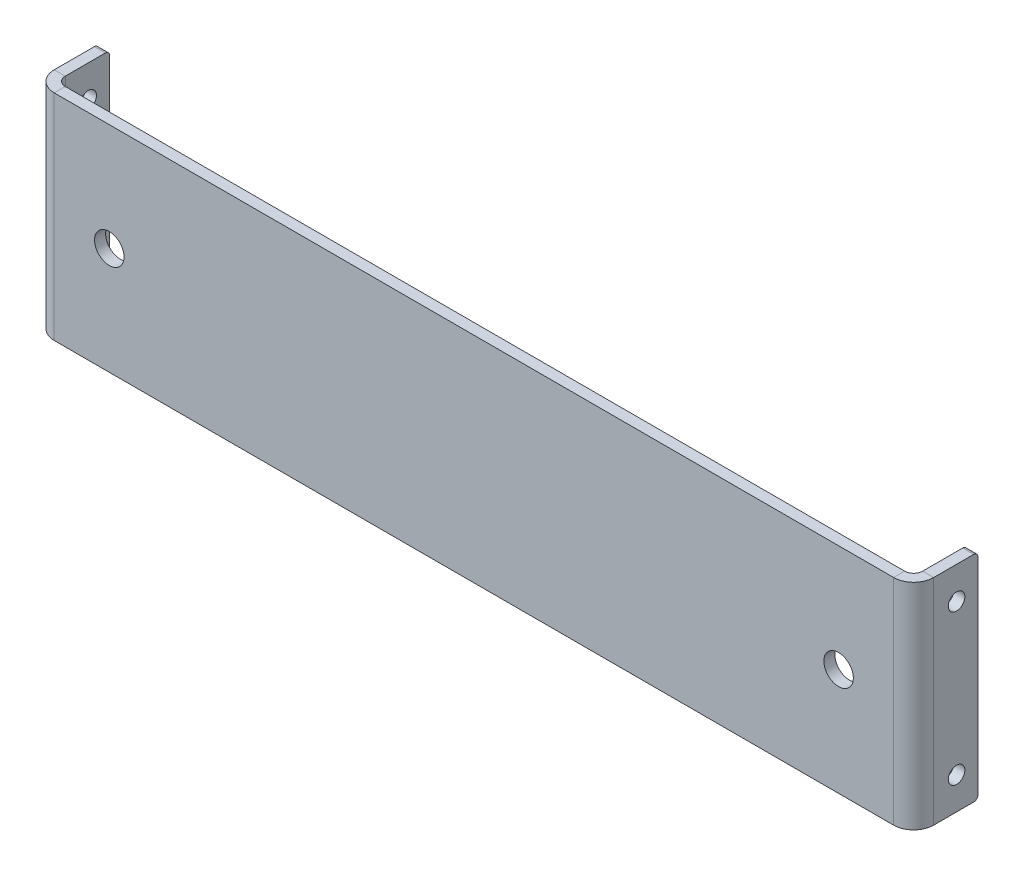
SolidWorks part; units mm, degrees
note: The reader was unsure of these and kept them because the rebuilt part matched: flange length of "Edge-Flange1".
ref_plane "Front Plane" through (0, 0, 0) normal (0, 0, 1) x (1, 0, 0)
ref_plane "Top Plane" through (0, 0, 0) normal (0, 1, 0) x (1, 0, 0)
ref_plane "Right Plane" through (0, 0, 0) normal (1, 0, 0) x (0, 0, -1)
sketch "Sketch1" plane through (0, 0, 0) normal (0, 0, 1) x (1, 0, 0)
  line L1 (-130.175, -31.75) -> (130.175, -31.75)
  line L2 (-130.175, -31.75) -> (-130.175, 31.75)
  line L3 (-130.175, 31.75) -> (130.175, 31.75)
  line L4 (130.175, -31.75) -> (130.175, 31.75)
  line L5 (-130.175, -31.75) -> (130.175, 31.75) construction
  line L6 (-130.175, 31.75) -> (130.175, -31.75) construction
  point P0 (0, 0)
  dimension "D1" = 260.35
  dimension "D2" = 63.5
base flange "Base-Flange1" sketch "Sketch1" thickness 3.2639 reverse thickness direction no parameters "D1"=2.6568
edge flange "Edge-Flange1" sketch "Sketch10" flange profiles "Sketch10", "Sketch11" flange angle 90 flange length 19.05 flange position material inside bend radius 2.6568 thickness 3.2639 relief rectangular parameters "D6"=10, "D8"=1
sketch "Sketch10" plane through (130.175, 0, -3.2639) normal (-1, 0, 0) x (0, 1, 0)
  line L2 (-31.75, 0) -> (-31.75, 15.7861)
  line L3 (-31.75, 15.7861) -> (31.75, 15.7861)
  line L4 (31.75, 15.7861) -> (31.75, 0)
  line L5 (31.75, 0) -> (-31.75, 0) construction
  line L6 (31.75, 0) -> (-31.75, 0)
sketch "Sketch11" plane through (-130.175, 0, -3.2639) normal (1, 0, 0) x (0, -1, 0)
  line L0 (31.75, 0) -> (-31.75, 0) construction
  line L1 (31.75, 0) -> (-31.75, 0)
  line L2 (31.75, 0) -> (31.75, 15.7861)
  line L3 (31.75, 15.7861) -> (-31.75, 15.7861)
  line L4 (-31.75, 15.7861) -> (-31.75, 0)
bend "EdgeBend1" bend radius 2.6568 bend angle 90 parameters "D5"=1
bend "EdgeBend2" bend radius 2.6568 bend angle 90 parameters "D5"=2
hole_wizard "#10 (0.1935) Diameter Hole1" positions "Sketch12" profile "Sketch13" hole size "#10" standard "ANSI Inch" end condition through all
sketch "Sketch12" plane through (130.175, 0, 0) normal (1, 0, 0) x (0, 0, -1)
  line L0 (0, -31.75) -> (0, 31.75) construction
  line L1 (5.9207, 31.75) -> (19.05, 31.75) construction
  line L2 (19.05, -31.75) -> (5.9207, -31.75) construction
  point P0 (12.7, 22.225)
  point P2 (12.7, -22.225)
  dimension "D1" = 12.7
  dimension "D2" = 9.525
  dimension "D3" = 9.525
sketch "Sketch13" plane through (130.175, 22.225, -12.7) normal (0, 1, 0) x (0, 0, -1)
  line L0 (0, 0) -> (0, 260.35)
  line L1 (0, 260.35) -> (2.4574, 260.35)
  line L2 (2.4574, 260.35) -> (2.4574, 0)
  line L5 (2.4574, 0) -> (0, 0)
  line L11 (0, -6.35) -> (0, 107.95) construction
  dimension "Thru Hole Dia." = 4.9149
  dimension "Thru Hole Depth" = 260.35
fillet "Fillet1" radius 1.27 4 edges at (-128.5431, 31.75, -19.05) (-128.5431, -31.75, -19.05) (128.5431, -31.75, -19.05) (128.5431, 31.75, -19.05)
hole_wizard "11/32 (0.34375) Diameter Hole1" positions "Sketch14" profile "Sketch15" hole size "11/32" standard "ANSI Inch" end condition through all
sketch "Sketch14" plane through (0, 0, 0) normal (0, 0, 1) x (1, 0, 0)
  line L0 (-124.2543, -31.75) -> (124.2543, -31.75) construction
  point P0 (-107.95, 0)
  point P2 (107.95, 0)
  dimension "D1" = 107.95
  dimension "D2" = 215.9
  dimension "D3" = 31.75
sketch "Sketch15" plane through (-107.95, 0, 0) normal (1, 0, 0) x (0, -1, 0)
  line L0 (0, 0) -> (0, 19.05)
  line L1 (0, 19.05) -> (4.3656, 19.05)
  line L2 (4.3656, 19.05) -> (4.3656, 0)
  line L5 (4.3656, 0) -> (0, 0)
  line L11 (0, -6.35) -> (0, 107.95) construction
  dimension "Thru Hole Dia." = 8.7312
  dimension "Thru Hole Depth" = 19.05
sketch "Bend-Lines1" [suppressed] plane through (0, 0, 0) normal (0, 1, 0) x (1, 0, 0)
sketch "Bounding-Box1" [suppressed] plane through (0, 0, 0) normal (0, 1, 0) x (1, 0, 0)
sheet metal parameters "Sheet-Metal1" thickness 3.2639 parameters "D1"=2.6568
flat pattern "Flat-Pattern1" [suppressed]
sketch "Bend-Lines2" plane through (0, 0, 0) normal (0, 1, 0) x (1, 0, 0)
sketch3d "Bounding-Box2" [suppressed]
  line L0 (130.175, -38.1, 0) -> (-130.175, -38.1, 0) construction
  line L1 (130.175, 38.1, 0) -> (-130.175, 38.1, 0) construction
  line L2 (130.175, -38.1, 0) -> (130.175, 38.1, 0) construction
  line L3 (-130.175, -38.1, 0) -> (-130.175, 38.1, 0) construction
sheet metal parameters "Sheet-Metal2" thickness 3.2639 parameters "D1"=2.6568
flat pattern "Flat-Pattern1"
sketch "Bend-Lines2" plane through (0, 0, 0) normal (0, 0, 1) x (1, 0, 0)
  line L0 (-127.6227, 38.1) -> (-127.6227, -38.1) construction
  line L1 (127.6227, -38.1) -> (127.6227, 38.1) construction
  line L2 (-127.6227, 38.1) -> (-127.6227, -38.1) construction
  line L3 (127.6227, -38.1) -> (127.6227, 38.1) construction
sketch3d "Bounding-Box2" [suppressed]
  line L0 (-144.1203, -38.1, 0) -> (144.1203, -38.1, 0) construction
  line L1 (-144.1203, 38.1, 0) -> (144.1203, 38.1, 0) construction
  line L2 (-144.1203, -38.1, 0) -> (-144.1203, 38.1, 0) construction
  line L3 (144.1203, -38.1, 0) -> (144.1203, 38.1, 0) construction
bend of the flat pattern "Flatten-<EdgeBend1>1"
bend of the flat pattern "Flatten-<EdgeBend2>1"
sheet metal parameters "Sheet-Metal3" thickness 3.2639 parameters "D1"=2.6568
flat pattern "Flat-Pattern1"
sketch "Bend-Lines2" plane through (0, 0, 0) normal (0, 0, 1) x (1, 0, 0)
  line L0 (-127.6227, 38.1) -> (-127.6227, -38.1) construction
  line L1 (127.6227, -38.1) -> (127.6227, 38.1) construction
  line L2 (-127.6227, 38.1) -> (-127.6227, -38.1) construction
  line L3 (127.6227, -38.1) -> (127.6227, 38.1) construction
sketch3d "Bounding-Box2" [suppressed]
  line L0 (-144.1203, -38.1, 0) -> (144.1203, -38.1, 0) construction
  line L1 (-144.1203, 38.1, 0) -> (144.1203, 38.1, 0) construction
  line L2 (-144.1203, -38.1, 0) -> (-144.1203, 38.1, 0) construction
  line L3 (144.1203, -38.1, 0) -> (144.1203, 38.1, 0) construction
bend of the flat pattern "Flatten-<EdgeBend1>1"
bend of the flat pattern "Flatten-<EdgeBend2>1"
sheet metal parameters "Sheet-Metal4" thickness 3.2639 parameters "D1"=2.6568
flat pattern "Flat-Pattern1"
sketch "Bend-Lines2" plane through (0, 0, 0) normal (0, 0, 1) x (1, 0, 0)
  line L0 (-127.6227, 31.75) -> (-127.6227, -31.75) construction
  line L1 (127.6227, -31.75) -> (127.6227, 31.75) construction
  line L2 (-127.6227, 31.75) -> (-127.6227, -31.75) construction
  line L3 (127.6227, -31.75) -> (127.6227, 31.75) construction
sketch3d "Bounding-Box2" [suppressed]
  line L0 (-144.1203, -31.75, 0) -> (144.1203, -31.75, 0) construction
  line L1 (-144.1203, 31.75, 0) -> (144.1203, 31.75, 0) construction
  line L2 (-144.1203, -31.75, 0) -> (-144.1203, 31.75, 0) construction
  line L3 (144.1203, -31.75, 0) -> (144.1203, 31.75, 0) construction
bend of the flat pattern "Flatten-<EdgeBend1>1"
bend of the flat pattern "Flatten-<EdgeBend2>1"
